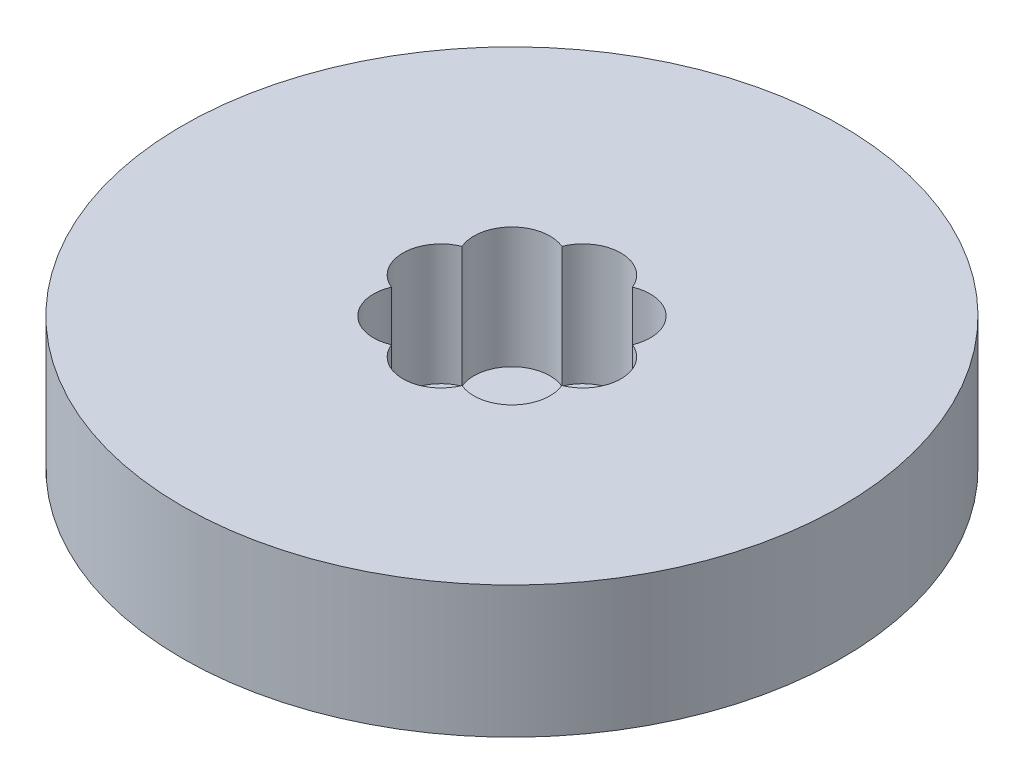
SolidWorks part; units mm, degrees
ref_plane "Front Plane" through (0, 0, 0) normal (0, 0, 1) x (1, 0, 0)
ref_plane "Top Plane" through (0, 0, 0) normal (0, 1, 0) x (1, 0, 0)
ref_plane "Right Plane" through (0, 0, 0) normal (1, 0, 0) x (0, 0, -1)
sketch "Sketch1" plane through (0, 0, 0) normal (0, 1, 0) x (1, 0, 0)
  circle A0 centre (0, 0) radius 27.5
  dimension "FLANGE_OD" = 55
extrude "Boss-Extrude1" add sketch "Sketch1" along normal blind 11
sketch "Sketch2" plane through (0, 0, 0) normal (0, 1, 0) x (1, 0, 0)
  circle A0 centre (0, 0) radius 5
  dimension "BORE_D" = 10
extrude "Cut-Extrude1" cut sketch "Sketch2" along normal through all
sketch "Sketch3" plane through (0, 11, 0) normal (0, 1, 0) x (1, 0, 0)
  circle A0 centre (0, 0) radius 5.921 construction
  circle A1 centre (-5.921, 0) radius 3.1767
  dimension "BOLT_D" = 6.3534
  dimension "BOLT_PCD" = 11.8419
extrude "Cut-Extrude2" cut sketch "Sketch3" against normal blind 10.1028
pattern_circular "CirPattern1" count 8 over 360 about axis through (0, 0, 0) along (0, 1, 0) of "Cut-Extrude2"
